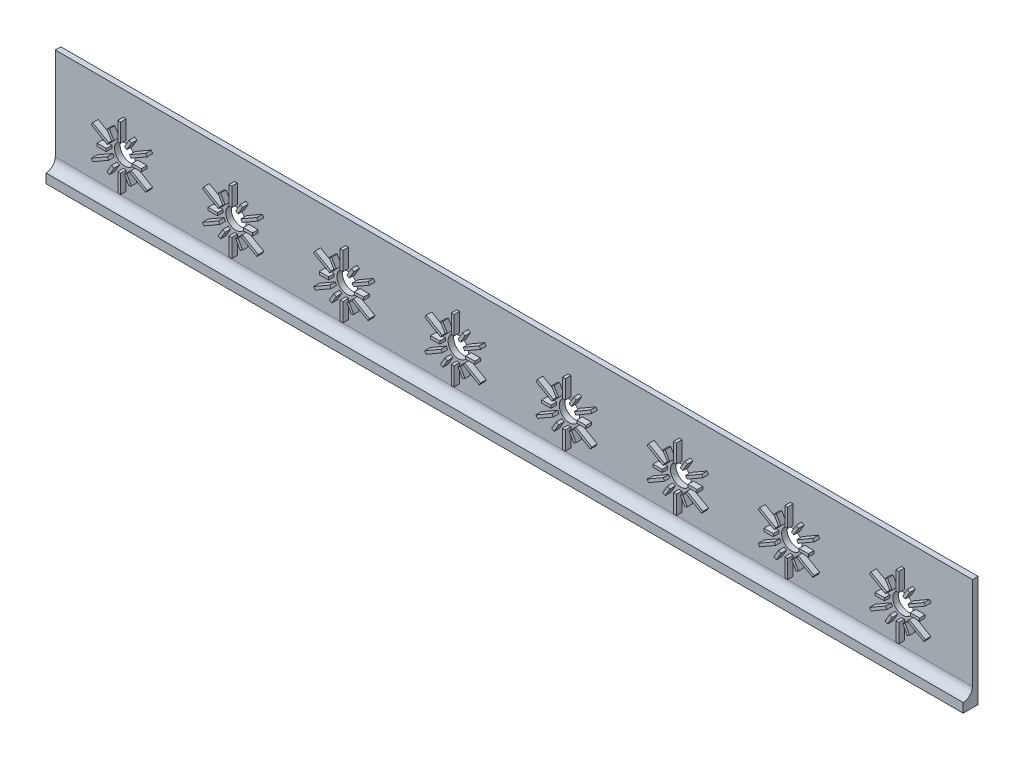
SolidWorks part; units mm, degrees
ref_plane "前视基准面" through (0, 0, 0) normal (0, 0, 1) x (1, 0, 0)
ref_plane "上视基准面" through (0, 0, 0) normal (0, 1, 0) x (1, 0, 0)
ref_plane "右视基准面" through (0, 0, 0) normal (1, 0, 0) x (0, 0, -1)
sketch "草图1" plane through (0, 0, 0) normal (0, 0, 1) x (1, 0, 0)
  line L1 (0, 0) -> (495, 0)
  line L2 (0, 0) -> (0, 60)
  line L3 (0, 60) -> (495, 60)
  line L4 (495, 0) -> (495, 60)
  dimension "D1" = 495
  dimension "D2" = 60
extrude "凸台-拉伸1" add sketch "草图1" along normal blind 3 contours L1 L4 L3 L2
sketch "草图2" plane through (0, 0, 0) normal (0, 0, -1) x (-1, 0, 0)
  line L0 (0, 30) -> (-495, 30) construction
  line L1 (0, 0) -> (0, 60) construction
  line L2 (-495, 0) -> (-495, 60) construction
  circle A0 centre (-37.5, 30) radius 5.5
  dimension "D2" = 11
  dimension "D1" = 37.5
extrude "切除-拉伸1" cut sketch "草图2" against normal through all
pattern_linear "阵列(线性)1" count 8 spacing 60 along (1, 0, 0) of "切除-拉伸1"
sketch "草图3" plane through (0, 0, 3) normal (0, 0, 1) x (1, 0, 0)
  line L5 (0, 0) -> (0, 60) construction
  line L6 (495, 0) -> (0, 0)
  line L7 (495, 0) -> (495, 5)
  line L8 (495, 5) -> (0, 5)
  line L9 (0, 0) -> (0, 5)
  dimension "D1" = 5
extrude "凸台-拉伸2" add sketch "草图3" along normal blind 5
fillet "圆角1" radius 5 1 edges at (247.5, 5, 3)
sketch "草图4" plane through (0, 0, 3) normal (0, 0, 1) x (1, 0, 0)
  line L0 (43.1523, 34.1294) -> (51.8125, 39.1294)
  line L4 (36.75, 46.9597) -> (38.25, 46.9597)
  line L5 (43.9023, 32.8303) -> (52.5625, 37.8303)
  line L6 (51.8125, 39.1294) -> (52.5625, 37.8303)
  line L7 (36.75, 36.9597) -> (36.75, 46.9597)
  line L8 (43.9023, 27.1697) -> (52.5625, 22.1697)
  line L9 (43.1523, 25.8706) -> (51.8125, 20.8706)
  line L10 (38.25, 36.9597) -> (38.25, 46.9597)
  line L11 (52.5625, 22.1697) -> (51.8125, 20.8706)
  line L12 (38.25, 23.0403) -> (38.25, 13.0403)
  line L13 (36.75, 23.0403) -> (36.75, 13.0403)
  line L14 (38.25, 13.0403) -> (36.75, 13.0403)
  line L15 (31.8477, 25.8706) -> (23.1875, 20.8706)
  line L16 (31.0977, 27.1697) -> (22.4375, 22.1697)
  line L17 (23.1875, 20.8706) -> (22.4375, 22.1697)
  line L18 (31.0977, 32.8303) -> (22.4375, 37.8303)
  line L19 (31.8477, 34.1294) -> (23.1875, 39.1294)
  line L20 (22.4375, 37.8303) -> (23.1875, 39.1294)
  circle A0 centre (37.5, 30) radius 5.5 construction
  arc A2 (38.25, 36.9597) -> (36.75, 36.9597) centre (37.5, 30) ccw
  arc A3 (43.9023, 32.8303) -> (43.1523, 34.1294) centre (37.5, 30) ccw
  arc A4 (43.1523, 25.8706) -> (43.9023, 27.1697) centre (37.5, 30) ccw
  arc A5 (36.75, 23.0403) -> (38.25, 23.0403) centre (37.5, 30) ccw
  arc A6 (31.0977, 27.1697) -> (31.8477, 25.8706) centre (37.5, 30) ccw
  arc A7 (31.8477, 34.1294) -> (31.0977, 32.8303) centre (37.5, 30) ccw
  point P30 (37.5, 30)
  dimension "D3" = 7
  dimension "D1" = 10
  dimension "D2" = 6
  dimension "D4" = 1.5
extrude "凸台-拉伸3" add sketch "草图4" along normal blind 3
sketch "草图5" plane through (0, 0, 3) normal (0, 0, 1) x (1, 0, 0)
  line L0 (42.8303, 40.7324) -> (40.3303, 36.4023)
  line L2 (41.6294, 35.6523) -> (44.1294, 39.9824)
  line L3 (42.8303, 40.7324) -> (44.1294, 39.9824)
  line L4 (49.4597, 30.75) -> (44.4597, 30.75)
  line L5 (44.4597, 29.25) -> (49.4597, 29.25)
  line L12 (49.4597, 30.75) -> (49.4597, 29.25)
  line L13 (44.1294, 20.0176) -> (41.6294, 24.3477)
  line L14 (40.3303, 23.5977) -> (42.8303, 19.2676)
  line L15 (44.1294, 20.0176) -> (42.8303, 19.2676)
  line L16 (32.1697, 19.2676) -> (34.6697, 23.5977)
  line L17 (33.3706, 24.3477) -> (30.8706, 20.0176)
  line L18 (32.1697, 19.2676) -> (30.8706, 20.0176)
  line L19 (25.5403, 29.25) -> (30.5403, 29.25)
  line L20 (30.5403, 30.75) -> (25.5403, 30.75)
  line L21 (25.5403, 29.25) -> (25.5403, 30.75)
  line L22 (30.8706, 39.9824) -> (33.3706, 35.6523)
  line L23 (34.6697, 36.4023) -> (32.1697, 40.7324)
  line L24 (30.8706, 39.9824) -> (32.1697, 40.7324)
  arc A0 (41.6294, 35.6523) -> (40.3303, 36.4023) centre (37.5, 30) ccw
  arc A1 (44.4597, 29.25) -> (44.4597, 30.75) centre (37.5, 30) ccw
  arc A4 (40.3303, 23.5977) -> (41.6294, 24.3477) centre (37.5, 30) ccw
  arc A5 (33.3706, 24.3477) -> (34.6697, 23.5977) centre (37.5, 30) ccw
  arc A6 (30.5403, 30.75) -> (30.5403, 29.25) centre (37.5, 30) ccw
  arc A7 (34.6697, 36.4023) -> (33.3706, 35.6523) centre (37.5, 30) ccw
  point P15 (37.5, 30)
  point P28 (37.5, 30)
  dimension "D1" = 6
extrude "凸台-拉伸4" add sketch "草图5" along normal up to surface (3 mm away) up to face at (27.1339, 35.9849, 6)
pattern_linear "阵列(线性)2" count 8 spacing 60 along (1, 0, 0) of "凸台-拉伸3", "凸台-拉伸4"
